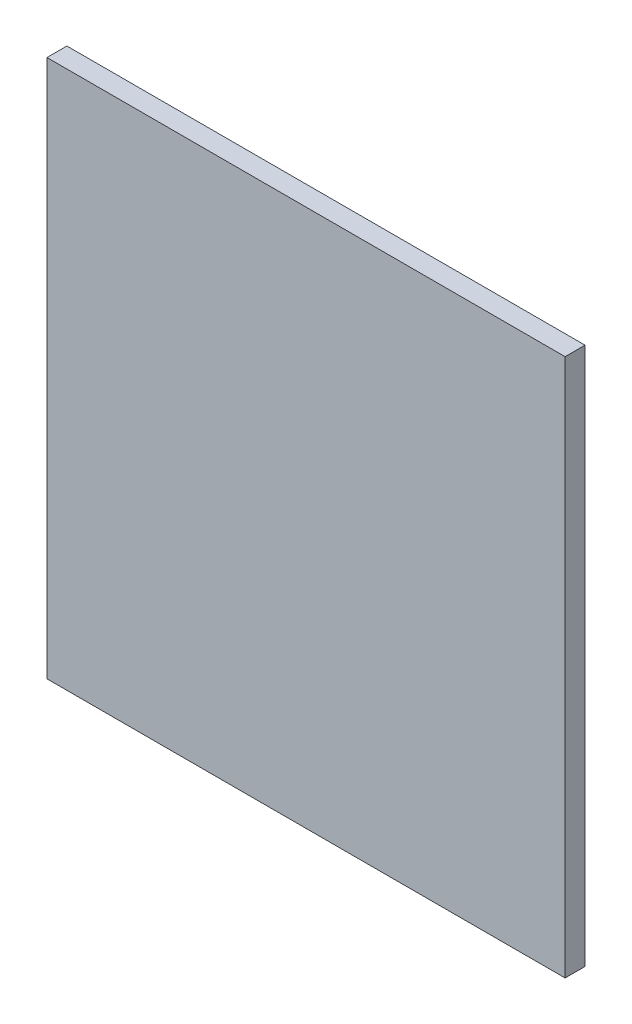
SolidWorks part; units mm, degrees
ref_plane "Front Plane" through (0, 0, 0) normal (0, 0, 1) x (1, 0, 0)
ref_plane "Top Plane" through (0, 0, 0) normal (0, 1, 0) x (1, 0, 0)
ref_plane "Right Plane" through (0, 0, 0) normal (1, 0, 0) x (0, 0, -1)
sketch "Sketch1" plane through (0, 0, 0) normal (0, 0, 1) x (1, 0, 0)
  line L0 (-6.35, 155.575) -> (-6.35, 130.175) construction
  line L1 (158.75, 155.575) -> (-6.35, 155.575)
  line L2 (158.75, 155.575) -> (158.75, -15.875)
  line L3 (158.75, -15.875) -> (-6.35, -15.875)
  line L4 (-6.35, 155.575) -> (-6.35, -15.875)
  line L6 (0, -15.875) -> (-6.35, -15.875) construction
extrude "Boss-Extrude1" add sketch "Sketch1" along normal blind 6.35
sketch "Sketch2" plane through (0, 0, 6.35) normal (0, 0, 1) x (1, 0, 0)
  line L0 (158.75, -15.875) -> (158.75, 155.575) construction
  line L1 (152.4, 130.175) -> (158.75, 130.175)
  line L2 (152.4, 130.175) -> (152.4, 104.775)
  line L3 (152.4, 104.775) -> (158.75, 104.775)
  line L4 (158.75, 130.175) -> (158.75, 104.775)
